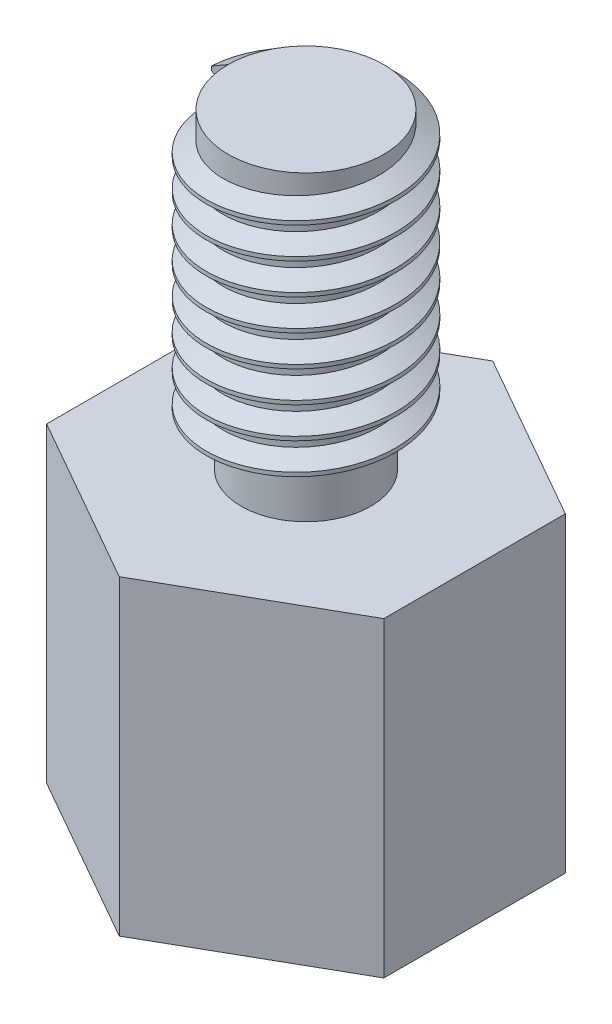
SolidWorks part; units mm, degrees
ref_plane "Plan de face" through (0, 0, 0) normal (0, 0, 1) x (1, 0, 0)
ref_plane "Plan de dessus" through (0, 0, 0) normal (0, 1, 0) x (1, 0, 0)
ref_plane "Plan de droite" through (0, 0, 0) normal (1, 0, 0) x (0, 0, -1)
sketch "Esquisse1" plane through (0, 0, 0) normal (0, 1, 0) x (1, 0, 0)
  line L0 (-3.25, 0) -> (3.25, 0) construction
  line L1 (0, 3.6) -> (0, -3.6) construction
  line L2 (-3.25, 1.75) -> (-3.25, -1.75)
  line L3 (0, 3.6) -> (-3.25, 1.75)
  line L4 (-3.25, -1.75) -> (0, -3.6)
  line L5 (3.25, -1.75) -> (0, -3.6)
  line L6 (3.25, 1.75) -> (3.25, -1.75)
  line L7 (0, 3.6) -> (3.25, 1.75)
  point P4 (0, 0)
  point P6 (0, 0)
  point P9 (-3.25, 0)
  dimension "D1" = 6.5
  dimension "D2" = 7.2
  dimension "D3" = 3.5
extrude "Boss.-Extru.1" add sketch "Esquisse1" along normal blind 6
sketch "Esquisse2" plane through (0, 0, 0) normal (0, -1, 0) x (1, 0, 0)
  circle A0 centre (0, 0) radius 1.5
  dimension "D1" = 3
extrude "Enlèv. mat.-Extru.1" cut sketch "Esquisse2" against normal blind 5
sketch "Esquisse3" plane through (0, 6, 0) normal (0, 1, 0) x (1, 0, 0)
  circle A0 centre (0, 0) radius 1.25
  dimension "D1" = 2.5
extrude "Boss.-Extru.2" add sketch "Esquisse3" along normal blind 6
sketch "Esquisse4" plane through (0, 12, 0) normal (0, 1, 0) x (1, 0, 0)
  circle A0 centre (0, 0) radius 1.5
  dimension "D1" = 3
extrude "Boss.-Extru.3" add sketch "Esquisse4" against normal blind 5
thread "Filetage1" pitch 0.6 method extrude profile "Profil de filetage1" start angle 0, offset 0, length 5, pitch 0.6, diameter 3
ref_plane "Plan1" through (-1.5, 12, 0) normal (0, 0, 1) x (-1, 0, 0)
sketch "Profil de filetage1" plane through (-1.5, 12, 0) normal (0, 0, 1) x (-1, 0, 0)
  line L0 (0, 0) -> (0, 0.6) construction
  line L1 (0, 0) -> (0.3248, 0.1875)
  line L2 (0.3248, 0.1875) -> (0.3248, 0.2625)
  line L3 (0.3248, 0.2625) -> (0, 0.45)
  line L4 (0.3248, 0.225) -> (0, 0.225) construction
  line L11 (0, 0) -> (0, 0.45)
  point P2 (0, 0)
  dimension "Pitch" = 0.6
  dimension "Profile_Angle" = 60
  dimension "Profile_Land" = 0.075
  dimension "Profile_Height" = 0.3248
thread "Filetage2" pitch 0.6 method cut profile "Profil de filetage2" start angle 0, offset 0, length 5, pitch 0.6, diameter 3
ref_plane "Plan2" through (1.5, 0, 0) normal (0, 0, 1) x (1, 0, 0)
sketch "Profil de filetage2" plane through (1.5, 0, 0) normal (0, 0, 1) x (1, 0, 0)
  line L0 (0, 0) -> (0, 0.6) construction
  line L1 (0, 0) -> (0.3248, 0.1875)
  line L2 (0.3248, 0.1875) -> (0.3248, 0.2625)
  line L3 (0.3248, 0.2625) -> (0, 0.45)
  line L4 (0.3248, 0.225) -> (0, 0.225) construction
  line L11 (0, 0) -> (0, 0.45)
  point P2 (0, 0)
  dimension "Pitch" = 0.6
  dimension "Profile_Angle" = 60
  dimension "Profile_Land" = 0.075
  dimension "Profile_Height" = 0.3248
